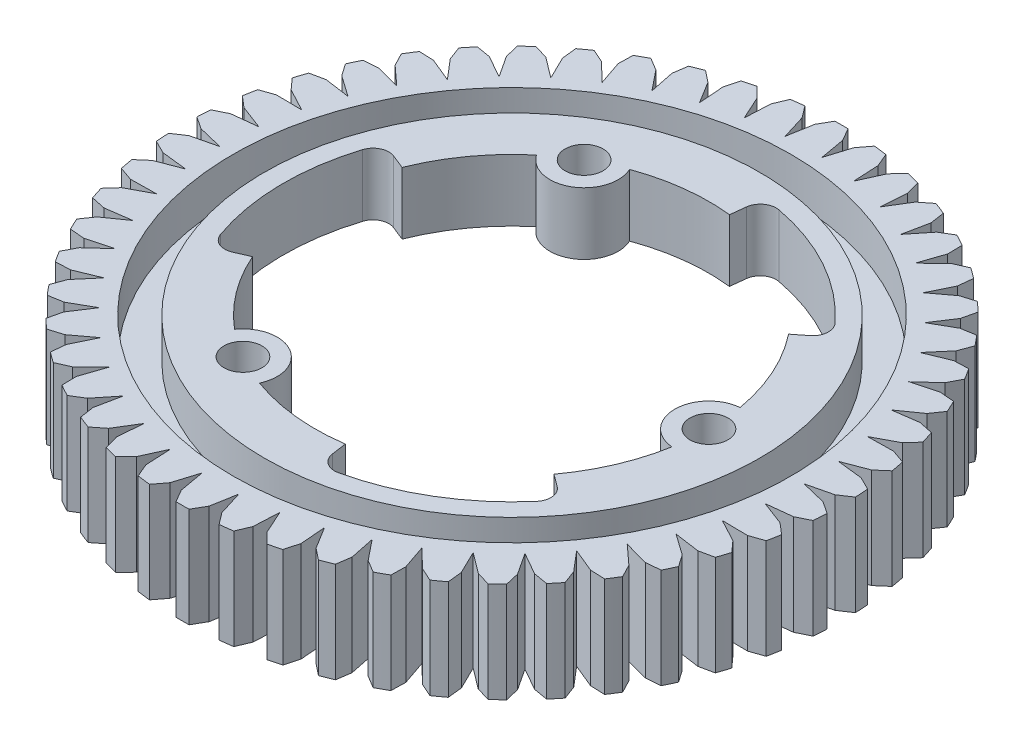
SolidWorks part; units mm, degrees
ref_plane "Front Plane" through (0, 0, 0) normal (0, 0, 1) x (1, 0, 0)
ref_plane "Top Plane" through (0, 0, 0) normal (0, 1, 0) x (1, 0, 0)
ref_plane "Right Plane" through (0, 0, 0) normal (1, 0, 0) x (0, 0, -1)
sketch "Sketch1" plane through (0, 0, 0) normal (0, 1, 0) x (1, 0, 0)
  line L0 (0, 0) -> (1.716, 15.445) construction
  line L1 (0, 0) -> (12.2062, 9.6177) construction
  line L2 (12.2062, 9.6177) -> (1.716, 15.445) construction
  line L3 (12.2062, 9.6177) -> (15.4676, 1.4983) construction
  line L4 (1.716, 15.445) -> (1.8489, 16.641)
  line L5 (12.2062, 9.6177) -> (13.1514, 10.3625)
  line L6 (0, 0) -> (13.5415, 7.6235) construction
  line L7 (13.5415, 7.6235) -> (13.5415, -7.6235) construction
  line L8 (13.5415, -7.6235) -> (0, 0) construction
  line L9 (13.5415, 7.6235) -> (14.5902, 8.2139)
  line L10 (13.5415, -7.6235) -> (14.5902, -8.2139)
  line L11 (0, 0) -> (19.54, 0) construction
  circle A0 centre (0, 0) radius 15.54
  circle A1 centre (0, 0) radius 19.54
  circle A2 centre (0, 0) radius 18.04
  circle A3 centre (0, 0) radius 15.54
  circle A4 centre (15.54, 0) radius 1.5
  circle A5 centre (15.54, 0) radius 2.7
  circle A6 centre (3.0913, 16.503) radius 1.25
  circle A7 centre (12.3778, 11.3443) radius 1.25
  circle A8 centre (15.2034, 7.1246) radius 1.25
  circle A9 centre (15.2034, -7.1246) radius 1.25
  point P24 (13.5415, 0)
  dimension "D1" = 31.08
  dimension "D2" = 4
  dimension "D3" = 1.5
  dimension "D4" = 3
  dimension "D5" = 1.2
  dimension "D6" = 12
  dimension "D8" = 2.4
  dimension "D7" = 8.75
extrude "Boss-Extrude1" add sketch "Sketch1" along normal blind 7.9 contours A1 | A0
extrude "Boss-Extrude2" add sketch "Sketch1<3>" along normal up to surface (7.9 mm away) contours A5 up to face at (0, 7.9, 19.54)
sketch "Sketch1<3>" plane through (0, 0, 0) normal (0, 1, 0) x (1, 0, 0) same geometry as "Sketch1"
extrude "Cut-Extrude1" cut sketch "Sketch1<4>" against normal through all both and the other way through all contours A4
sketch "Sketch1<4>" plane through (0, 0, 0) normal (0, 1, 0) x (1, 0, 0) same geometry as "Sketch1"
extrude "Cut-Extrude2" cut sketch "Sketch1<5>" against normal through all both and the other way through all contours A6 L4 A3 | A6 | A7 A2 A6 A3 | A7 | A7 A0 L5 region at (2.0013, 0, -15.6802) region at (3.0913, 0, -16.503) region at (8.0751, 0, -14.5367) region at (12.2552, 0, -9.9842) region at (12.3778, 0, -11.3443)
sketch "Sketch1<5>" plane through (0, 0, 0) normal (0, 1, 0) x (1, 0, 0) same geometry as "Sketch1"
extrude "Cut-Extrude5" cut sketch "Sketch1<6>" along normal blind 3 contours A8 L9 A0 | A8 | A8 A3 A5 A2 | A2 A5 A0 A4 A3 | A9 A2 A5 A3 | A9 | A9 A0 L10 | A5 | A0 region at (13.8991, 0, 7.5292) region at (15.2034, 0, 7.1246) region at (16.3146, 0, 4.2837) region at (15.458, 0, 2.1038) region at (16.3146, 0, -4.2837) region at (15.2034, 0, -7.1246) region at (13.8991, 0, -7.5292)
sketch "Sketch1<6>" plane through (0, 0, 0) normal (0, 1, 0) x (1, 0, 0) same geometry as "Sketch1"
pattern_circular "CirPattern1" count 3 over 360 about axis through (0, 7.9, 0) along (0, -1, 0) of "Boss-Extrude2", "Cut-Extrude1", "Cut-Extrude2", "Cut-Extrude5"
sketch "Sketch2" plane through (0, 0, 0) normal (0, 1, 0) x (1, 0, 0)
  circle A0 centre (0, 0) radius 26
  circle A1 centre (0, 0) radius 19.54
  circle A2 centre (0, 0) radius 22
  circle A3 centre (0, 0) radius 19.54 construction
  dimension "D1" = 52
  dimension "D2" = 4
extrude "Boss-Extrude3" add sketch "Sketch2" along normal up to surface (7.9 mm away) contours A0 | A1 up to face at (-9.069, 7.9, 12.708)
extrude "Cut-Extrude4" cut sketch "Sketch2<3>" against normal blind 3.14 from surface contours A2 | A1 starting at face at (-9.069, 7.9, 12.708)
sketch "Sketch2<3>" plane through (0, 0, 0) normal (0, 1, 0) x (1, 0, 0) same geometry as "Sketch2"
extrude "Cut-Extrude6" cut sketch "Sketch2<4>" along normal blind 3 contours A2
sketch "Sketch2<4>" plane through (0, 0, 0) normal (0, 1, 0) x (1, 0, 0) same geometry as "Sketch2"
sketch "Sketch3" plane through (0, 0, 0) normal (0, 1, 0) x (1, 0, 0)
  line L0 (-1.447, 23) -> (-1.0953, 24.9948) construction
  line L2 (0, 26) -> (0, 0) construction
  line L4 (-1.447, 23) -> (1.447, 23) construction
  line L5 (-1.0953, 24.9948) -> (-0.5179, 25.9948) construction
  line L6 (1.0953, 24.9948) -> (0.5179, 25.9948)
  line L7 (1.447, 23) -> (1.0953, 24.9948)
  line L8 (-1.447, 23) -> (0, 0) construction
  line L9 (0, 0) -> (1.447, 23) construction
  line L10 (2.046, 24.935) -> (2.7442, 25.8548)
  line L11 (1.447, 23) -> (2.046, 24.935)
  circle A0 centre (0, 0) radius 26 construction
  arc A1 (0.5179, 25.9948) -> (-0.5179, 25.9948) centre (0, 0) ccw construction
  arc A3 (0.5179, 25.9948) -> (2.7442, 25.8548) centre (0, 0) cw
  point P10 (0, 0)
  point P12 (0, 0)
  point P16 (0, 23)
  dimension "D1" = 7.2
  dimension "D2" = 3
  dimension "D3" = 80
  dimension "D4" = 160
  dimension "D5" = 1
extrude "Cut-Extrude7" cut sketch "Sketch3" along normal through all both and the other way through all
sketch "Sketch4" plane through (0, 0, 0) normal (0, 1, 0) x (1, 0, 0)
  point P0 (0, 24.497)
  point P2 (3.0703, 24.3038)
  point P3 (6.0922, 23.7274)
  point P5 (9.0179, 22.7767)
  point P8 (11.8015, 21.4669)
  point P9 (14.399, 19.8185)
  point P10 (16.7693, 17.8575)
  point P11 (18.8753, 15.615)
  point P12 (20.6835, 13.1261)
  point P13 (22.1655, 10.4303)
  point P14 (23.298, 7.57)
  point P15 (24.0631, 4.5903)
  point P16 (24.4486, 1.5382)
  point P17 (24.4486, -1.5382)
  point P18 (24.0631, -4.5903)
  point P19 (23.298, -7.57)
  point P20 (22.1655, -10.4303)
  point P21 (20.6835, -13.1261)
  point P22 (18.8753, -15.615)
  point P23 (16.7693, -17.8575)
  point P24 (14.399, -19.8185)
  point P25 (11.8015, -21.4669)
  point P26 (9.0179, -22.7767)
  point P27 (6.0922, -23.7274)
  point P28 (3.0703, -24.3038)
  point P29 (0, -24.497)
  point P30 (-3.0703, -24.3038)
  point P31 (-6.0922, -23.7274)
  point P32 (-9.0179, -22.7767)
  point P33 (-11.8015, -21.4669)
  point P34 (-14.399, -19.8185)
  point P35 (-16.7693, -17.8575)
  point P36 (-18.8753, -15.615)
  point P37 (-20.6835, -13.1261)
  point P38 (-22.1655, -10.4303)
  point P39 (-23.298, -7.57)
  point P40 (-24.0631, -4.5903)
  point P41 (-24.4486, -1.5382)
  point P42 (-24.4486, 1.5382)
  point P43 (-24.0631, 4.5903)
  point P44 (-23.298, 7.57)
  point P45 (-22.1655, 10.4303)
  point P46 (-20.6835, 13.1261)
  point P47 (-18.8753, 15.615)
  point P48 (-16.7693, 17.8575)
  point P49 (-14.399, 19.8185)
  point P50 (-11.8015, 21.4669)
  point P51 (-9.0179, 22.7767)
  point P52 (-6.0922, 23.7274)
  point P53 (-3.0703, 24.3038)
  point P54 (0, 0)
  dimension "D1" = 50
pattern_circular "CirPattern2" count 50 over 360 about axis through (0, 81.4391, 0) along (0, -1, 0) of "Cut-Extrude7"
